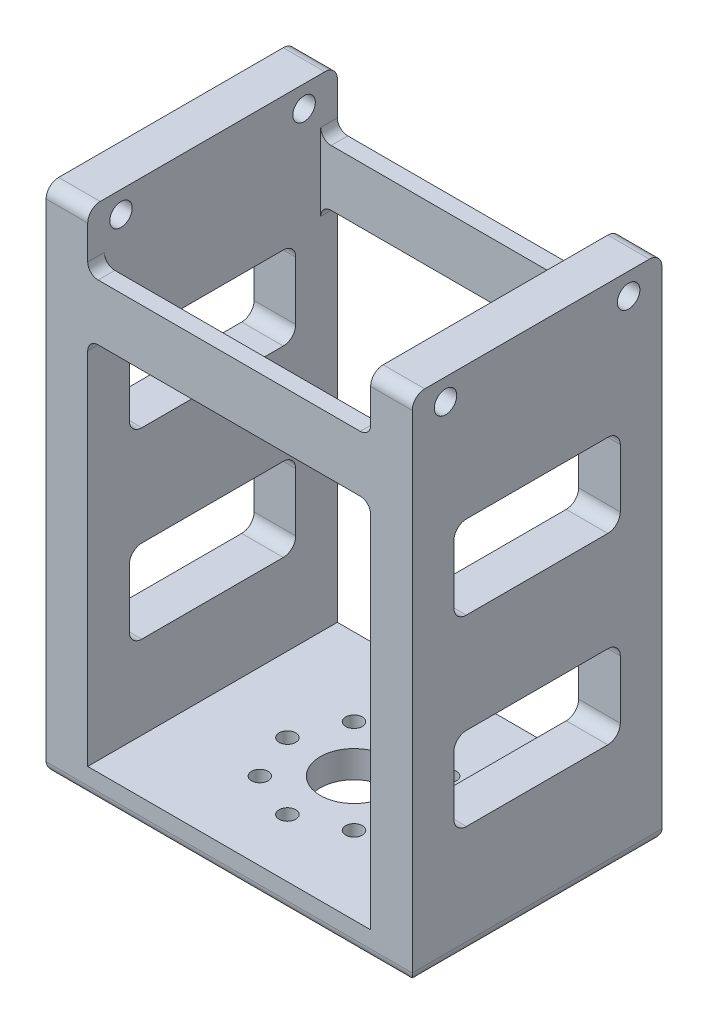
SolidWorks part; units mm, degrees
ref_plane "Front Plane" through (0, 0, 0) normal (0, 0, 1) x (1, 0, 0)
ref_plane "Top Plane" through (0, 0, 0) normal (0, 1, 0) x (1, 0, 0)
ref_plane "Right Plane" through (0, 0, 0) normal (1, 0, 0) x (0, 0, -1)
sketch "Sketch1" plane through (0, 0, 0) normal (0, 1, 0) x (1, 0, 0)
  line L1 (0, 0) -> (44, 0)
  line L2 (0, 0) -> (0, 30)
  line L3 (0, 30) -> (44, 30)
  line L4 (44, 0) -> (44, 30)
  dimension "D1" = 30
  dimension "D2" = 44
extrude "Boss-Extrude1" add sketch "Sketch1" along normal blind 54.5
sketch "Sketch5" plane through (0, 54.5, 0) normal (0, 1, 0) x (1, 0, 0)
  line L0 (0, 0) -> (44, 0) construction
  line L1 (0, 30) -> (5, 30)
  line L2 (0, 30) -> (0, 0)
  line L3 (0, 0) -> (5, 0)
  line L4 (5, 30) -> (5, 0)
  dimension "D1" = 5
ref_plane "Plane1" through (22, 0, 0) normal (-1, 0, 0) x (0, 0, 1)
extrude "Boss-Extrude3" add sketch "Sketch5" along normal blind 6.8
sketch "Sketch9" plane through (5, 0, 0) normal (1, 0, 0) x (0, 0, -1)
  line L0 (30, 61.3) -> (30, 54.5) construction
  line L2 (0, 61.3) -> (0, 54.5) construction
  line L4 (0, 61.3) -> (30, 61.3) construction
  circle A0 centre (26, 58.7) radius 1.35
  circle A1 centre (4, 58.7) radius 1.35
  dimension "D1" = 2.7
  dimension "D2" = 4
  dimension "D3" = 2.6
  dimension "D4" = 2.7
  dimension "D5" = 4
  dimension "D6" = 2.6
extrude "Cut-Extrude6" cut sketch "Sketch9" against normal through all
mirror "Mirror2" about plane through (22, 0, 0) normal (-1, 0, 0) of "Boss-Extrude3", "Cut-Extrude6"
fillet "Fillet1" radius 1.5 4 edges at (41.5, 61.3, -30) (2.5, 61.3, -30) (2.5, 61.3, 0) (41.5, 61.3, 0)
fillet "Fillet2" radius 1.25 4 edges at (0, 0, -15) (22, 0, -30) (22, 0, 0) (44, 0, -15)
sketch "Sketch11" plane through (0, 54.5, 0) normal (0, 1, 0) x (1, 0, 0)
  line L0 (39, 0) -> (39, 30) construction
  line L1 (39, 28) -> (5, 28)
  line L2 (39, 28) -> (39, 2)
  line L3 (39, 2) -> (5, 2)
  line L4 (5, 28) -> (5, 2)
  line L5 (5, 0) -> (5, 30) construction
  line L6 (39, 30) -> (5, 30) construction
  line L7 (5, 0) -> (39, 0) construction
  dimension "D1" = 2
  dimension "D2" = 2
extrude "Cut-Extrude7" cut sketch "Sketch11" against normal blind 51.25
ref_point "Point1"
sketch "Sketch13" plane through (0, 0, 0) normal (0, -1, 0) x (1, 0, 0)
  circle A0 centre (22, -15) radius 4.05
  circle A1 centre (30, -15) radius 1
  dimension "D1" = 8.1
  dimension "D2" = 2
  dimension "D3" = 8
extrude "Cut-Extrude8" cut sketch "Sketch13" against normal up to next
ref_axis "Axis1" through (22, 0, -15) along (0, -1, 0)
pattern_circular "CirPattern1" count 8 over 360 about axis through (22, 0, -15) along (0, -1, 0) of "Cut-Extrude8"
ref_plane "Plane2" through (0, 0, -15) normal (0, 0, -1) x (-1, 0, 0)
sketch "Sketch15" plane through (44, 0, 0) normal (1, 0, 0) x (0, 0, -1)
  line L0 (0, 1.25) -> (30, 1.25) construction
  line L1 (25, 13.25) -> (5, 13.25)
  line L2 (25, 13.25) -> (25, 23.25)
  line L3 (25, 23.25) -> (5, 23.25)
  line L4 (5, 13.25) -> (5, 23.25)
  line L5 (30, 59.8) -> (30, 1.25) construction
  line L6 (0, 59.8) -> (0, 1.25) construction
  line L8 (25, 35.25) -> (5, 35.25)
  line L9 (25, 35.25) -> (25, 45.25)
  line L10 (25, 45.25) -> (5, 45.25)
  line L11 (5, 35.25) -> (5, 45.25)
  dimension "D1" = 12
  dimension "D2" = 10
  dimension "D3" = 5
  dimension "D4" = 5
  dimension "D5" = 12
  dimension "D6" = 10
extrude "Cut-Extrude10" cut sketch "Sketch15" against normal up to next
fillet "Fillet6" radius 1.5 8 edges at (41.5, 13.25, -5) (41.5, 35.25, -5) (41.5, 23.25, -5) (41.5, 45.25, -5) (41.5, 23.25, -25) (41.5, 45.25, -25) (41.5, 35.25, -25) (41.5, 13.25, -25)
mirror "Mirror4" about plane through (22, 0, 0) normal (-1, 0, 0) of "Cut-Extrude10", "Fillet6"
sketch "Sketch16" plane through (0, 0, 0) normal (0, 0, 1) x (1, 0, 0)
  line L0 (42.75, 0) -> (1.25, 0) construction
  line L1 (5, 47.75) -> (39, 47.75)
  line L2 (5, 47.75) -> (5, 3.25)
  line L3 (5, 3.25) -> (39, 3.25)
  line L4 (39, 47.75) -> (39, 3.25)
  line L6 (5, 54.5) -> (39, 54.5) construction
  dimension "D1" = 3.25
  dimension "D2" = 6.75
extrude "Cut-Extrude11" cut sketch "Sketch16" against normal up to next
mirror "Mirror5" about plane through (0, 0, -15) normal (0, 0, -1) of "Cut-Extrude11"
fillet "Fillet7" radius 1.25 8 edges at (5, 47.75, -29) (5, 47.75, -1) (5, 54.5, -1) (5, 54.5, -29) (39, 54.5, -1) (39, 54.5, -29) (39, 47.75, -29) (39, 47.75, -1)
